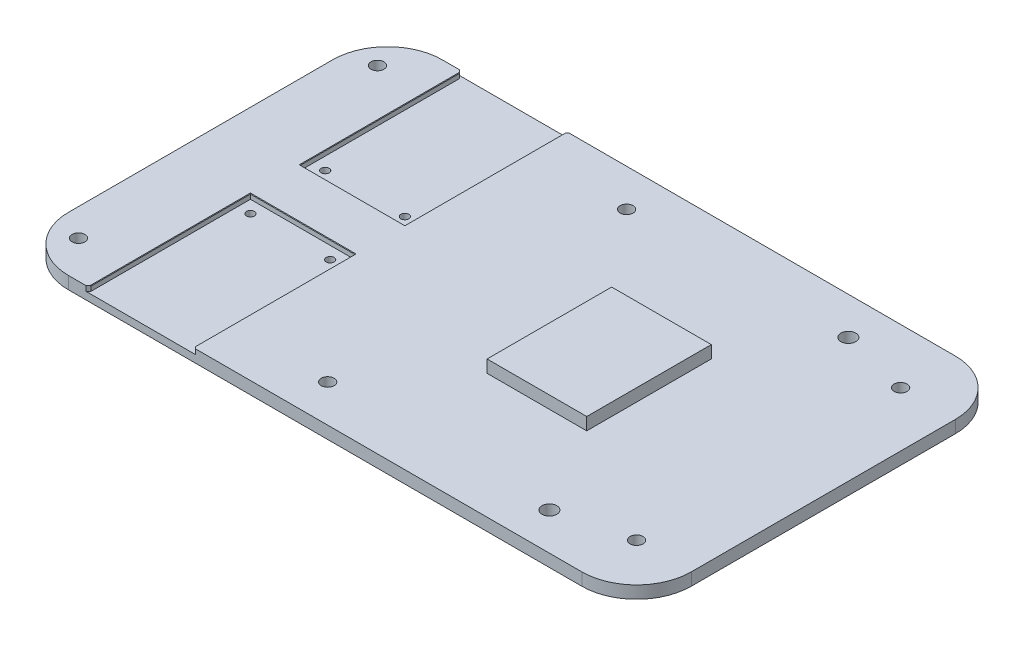
SolidWorks part; units mm, degrees
ref_plane "前视基准面" through (0, 0, 0) normal (0, 0, 1) x (1, 0, 0)
ref_plane "上视基准面" through (0, 0, 0) normal (0, 1, 0) x (1, 0, 0)
ref_plane "右视基准面" through (0, 0, 0) normal (1, 0, 0) x (0, 0, -1)
other "Configuration Table"
sketch "草图1" plane through (0, 0, 0) normal (0, 1, 0) x (1, 0, 0)
  line L0 (103, 75) -> (-103, 75)
  line L5 (-125, 53) -> (-125, -53)
  line L6 (-103, -75) -> (103, -75)
  line L7 (125, -53) -> (125, 53)
  line L8 (-1000, 0) -> (49000, 0) construction
  arc A0 (125, 53) -> (103, 75) centre (103, 53) ccw
  arc A1 (-103, 75) -> (-125, 53) centre (-103, 53) ccw
  arc A2 (-125, -53) -> (-103, -75) centre (-103, -53) ccw
  arc A3 (103, -75) -> (125, -53) centre (103, -53) ccw
  circle A4 centre (-114, 60) radius 2.6
  circle A5 centre (-14, 60) radius 2.6
  circle A6 centre (103, 53) radius 2.6
  circle A7 centre (-114, -60) radius 2.6
  circle A8 centre (-14, -60) radius 2.6
  circle A9 centre (103, -53) radius 2.6
  circle A10 centre (75, -60) radius 3
  circle A11 centre (75, 60) radius 3
  dimension "D3" = 22
  dimension "D4" = 22
  dimension "D5" = 22
  dimension "D6" = 22
  dimension "D9" = 100
  dimension "D10" = 117
  dimension "D11" = 106
  dimension "D12" = 117
  dimension "D13" = 100
  dimension "D14" = 120
  dimension "D15" = 7
  dimension "D16" = 11
  dimension "D17" = 50
  dimension "D18" = 15
  dimension "D19" = 6
  dimension "D1" = 150
  dimension "D2" = 250
  dimension "D7" = 125
  dimension "D8" = 75
extrude "凸台-拉伸1" add sketch "草图1" along normal blind 5
sketch "草图2" plane through (0, 5, 0) normal (0, 1, 0) x (1, 0, 0)
  line L0 (-103, -75) -> (103, -75) construction
  line L1 (-95, -75) -> (-53, -75)
  line L2 (-95, -75) -> (-95, -10)
  line L3 (-95, -10) -> (-53, -10)
  line L4 (-53, -75) -> (-53, -10)
  line L5 (-125, 53) -> (-125, -53) construction
  line L6 (-1000, 0) -> (49000, 0) construction
  line L7 (-53, 75) -> (-53, 10)
  line L8 (-95, 10) -> (-53, 10)
  line L9 (-95, 75) -> (-95, 10)
  line L10 (-95, 75) -> (-53, 75)
  dimension "D1" = 42
  dimension "D2" = 30
  dimension "D3" = 65
extrude "切除-拉伸1" cut sketch "草图2" against normal blind 2
chamfer "倒角1" distance 0.2 angle 45 6 edges at (-53, 5, -42.5) (-74, 5, -10) (-95, 5, -42.5) (-53, 5, 42.5) (-74, 5, 10) (-95, 5, 42.5)
chamfer "倒角2" distance 1 angle 45 4 edges at (-53, 3.9, 75) (-95, 3.9, 75) (-95, 3.9, -75) (-53, 3.9, -75)
sketch "草图3" plane through (0, 3, 0) normal (0, 1, 0) x (1, 0, 0)
  line L0 (-1000, 0) -> (49000, 0) construction
  line L1 (-95, 10) -> (-53, 10) construction
  line L2 (-53, 10) -> (-53, 74) construction
  line L3 (-95, 74) -> (-95, 10) construction
  circle A0 centre (-90, 15) radius 1.6
  circle A1 centre (-58, 15) radius 1.6
  circle A2 centre (-58, -15) radius 1.6
  circle A3 centre (-90, -15) radius 1.6
  dimension "D1" = 3.2
  dimension "D2" = 3.2
  dimension "D3" = 5
  dimension "D4" = 5
  dimension "D5" = 5
  dimension "D6" = 5
extrude "切除-拉伸2" cut sketch "草图3" against normal blind 3
sketch "草图4" plane through (0, 5, 0) normal (0, 1, 0) x (1, 0, 0)
  line L0 (-1000, 0) -> (49000, 0) construction
  line L1 (0, -1000) -> (0, 49000) construction
  line L3 (15, -25) -> (55, -25)
  line L4 (15, -25) -> (15, 25)
  line L5 (15, 25) -> (55, 25)
  line L6 (55, -25) -> (55, 25)
  line L7 (15, -25) -> (55, 25) construction
  line L8 (15, 25) -> (55, -25) construction
  point P4 (35, 0)
  dimension "D1" = 50
  dimension "D2" = 40
  dimension "D3" = 15
extrude "凸台-拉伸2" add sketch "草图4" along normal blind 5
